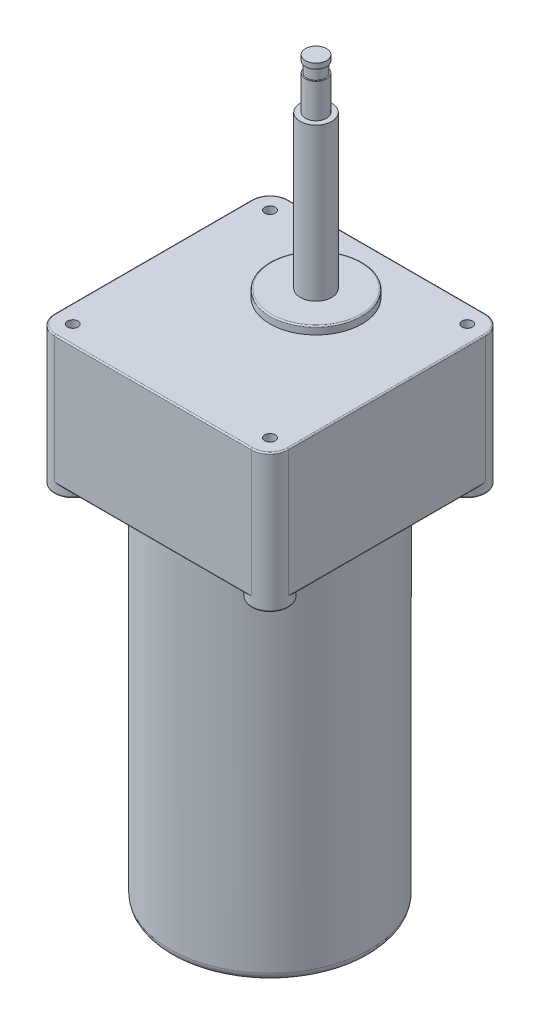
SolidWorks part; units mm, degrees
ref_plane "Front Plane" through (0, 0, 0) normal (0, 0, 1) x (1, 0, 0)
ref_plane "Top Plane" through (0, 0, 0) normal (0, 1, 0) x (1, 0, 0)
ref_plane "Right Plane" through (0, 0, 0) normal (1, 0, 0) x (0, 0, -1)
sketch "Sketch1" plane through (0, 0, 0) normal (0, 1, 0) x (1, 0, 0)
  circle A0 centre (0, 0) radius 38
  dimension "D1" = 76
extrude "Boss-Extrude1" add sketch "Sketch1" along normal blind 141
fillet "Fillet1" radius 3 1 edges at (0, 0, 38)
sketch "Sketch2" plane through (0, 141, 0) normal (0, 1, 0) x (1, 0, 0)
  line L1 (44.5, -44.5) -> (-44.5, -44.5)
  line L2 (44.5, -44.5) -> (44.5, 44.5)
  line L3 (44.5, 44.5) -> (-44.5, 44.5)
  line L4 (-44.5, -44.5) -> (-44.5, 44.5)
  line L5 (44.5, -44.5) -> (-44.5, 44.5) construction
  line L6 (44.5, 44.5) -> (-44.5, -44.5) construction
  point P0 (0, 0)
  dimension "D1" = 89
extrude "Boss-Extrude2" add sketch "Sketch2" along normal blind 49
fillet "Fillet2" radius 7 4 edges at (44.5, 165.5, 44.5) (44.5, 165.5, -44.5) (-44.5, 165.5, 44.5) (-44.5, 165.5, -44.5)
sketch "Sketch4" plane through (0, 141, 0) normal (0, -1, 0) x (1, 0, 0)
  line L0 (0, 0) -> (-42.4497, 42.4497) construction
  line L1 (-42.4497, 32.5503) -> (-31.36, 21.4605)
  line L2 (-32.5503, 42.4497) -> (-21.4605, 31.36)
  line L5 (32.5503, 42.4497) -> (21.4605, 31.36)
  line L6 (42.4497, 32.5503) -> (31.36, 21.4605)
  line L7 (42.4497, -32.5503) -> (31.36, -21.4605)
  line L8 (32.5503, -42.4497) -> (21.4605, -31.36)
  line L9 (-32.5503, -42.4497) -> (-21.4605, -31.36)
  line L10 (-42.4497, -32.5503) -> (-31.36, -21.4605)
  line L11 (-37.5, 44.5) -> (37.5, 44.5) construction
  arc A0 (-37.5, 44.5) -> (-44.5, 37.5) centre (-37.5, 37.5) ccw construction
  circle A3 centre (0, 0) radius 38 construction
  arc A4 (-21.4605, 31.36) -> (-31.36, 21.4605) centre (0, 0) ccw
  arc A5 (-32.5503, 42.4497) -> (-42.4497, 32.5503) centre (-37.5, 37.5) ccw
  arc A6 (31.36, 21.4605) -> (21.4605, 31.36) centre (0, 0) ccw
  arc A7 (42.4497, 32.5503) -> (32.5503, 42.4497) centre (37.5, 37.5) ccw
  arc A8 (21.4605, -31.36) -> (31.36, -21.4605) centre (0, 0) ccw
  arc A9 (32.5503, -42.4497) -> (42.4497, -32.5503) centre (37.5, -37.5) ccw
  arc A10 (-31.36, -21.4605) -> (-21.4605, -31.36) centre (0, 0) ccw
  arc A11 (-42.4497, -32.5503) -> (-32.5503, -42.4497) centre (-37.5, -37.5) ccw
  point P32 (0, 0)
  dimension "D1" = 4
  dimension "D2" = 7
extrude "Boss-Extrude3" add sketch "Sketch4" along normal blind 3.5
fillet "Fillet3" radius 0.5 24 edges at (42.4497, 190, 42.4497) (0, 190, 44.5) (-42.4497, 190, 42.4497) (-44.5, 190, 0) (-42.4497, 190, -42.4497) (0, 190, -44.5) (42.4497, 190, -42.4497) (-36.9049, 137.5, -27.0054) (-27.0054, 137.5, -36.9049) (-27.0054, 137.5, 36.9049) (-36.9049, 137.5, 27.0054) (27.0054, 137.5, -36.9049) (36.9049, 137.5, -27.0054) (27.0054, 137.5, 36.9049) (42.4497, 137.5, 42.4497) (44.5, 190, 0) (-44.5, 141, 0) (-42.4497, 137.5, -42.4497) (0, 141, -44.5) (0, 141, 44.5) (-42.4497, 137.5, 42.4497) (42.4497, 137.5, -42.4497) (36.9049, 137.5, 27.0054) (44.5, 141, 0)
sketch "Sketch3" plane through (0, 190, 0) normal (0, 1, 0) x (1, 0, 0)
  line L0 (0, -44.5) -> (0, 44.5) construction
  line L1 (37.5, 44.5) -> (-37.5, 44.5) construction
  line L2 (44.5, 0) -> (-44.5, 0) construction
  line L3 (-44.5, 37.5) -> (-44.5, -37.5) construction
  circle A0 centre (-37.5, 37.5) radius 2
  circle A2 centre (37.5, 37.5) radius 2
  circle A5 centre (37.5, -37.5) radius 2
  circle A6 centre (-37.5, -37.5) radius 2
  arc A8 (-37.5, 44.5) -> (-44.5, 37.5) centre (-37.5, 37.5) ccw construction
  point P11 (0, 0)
  point P17 (0, 0)
  dimension "D1" = 4
extrude "Cut-Extrude3" cut sketch "Sketch3" against normal through all
sketch "Sketch5" plane through (0, 190, 0) normal (0, 1, 0) x (1, 0, 0)
  line L0 (37.5, 44) -> (-37.5, 44) construction
  circle A0 centre (0, 17.5) radius 6
  dimension "D1" = 12
  dimension "D2" = 26.5
extrude "Boss-Extrude4" add sketch "Sketch5" along normal blind 80
sketch "Sketch6" plane through (0, 270, 0) normal (0, 1, 0) x (1, 0, 0)
  circle A0 centre (0, 17.5) radius 4
  circle A1 centre (0, 17.5) radius 6 construction
  dimension "D1" = 8
extrude "Cut-Extrude4" cut sketch "Sketch6" against normal blind 19 flip side to cut
ref_plane "Plane1" through (0, 268, 0) normal (0, 1, 0) x (1, 0, 0)
sketch "Sketch7" plane through (0, 268, 0) normal (0, 1, 0) x (1, 0, 0)
  circle A0 centre (0, 17.5) radius 3.5
  dimension "D1" = 7
extrude "Cut-Extrude5" cut sketch "Sketch7" against normal blind 4 flip side to cut
sketch "Sketch8" plane through (0, 190, 0) normal (0, 1, 0) x (1, 0, 0)
  circle A0 centre (0, 17.5) radius 17.5
  dimension "D1" = 35
extrude "Boss-Extrude5" add sketch "Sketch8" along normal blind 3
fillet "Fillet4" radius 0.5 1 edges at (0, 193, 0)
